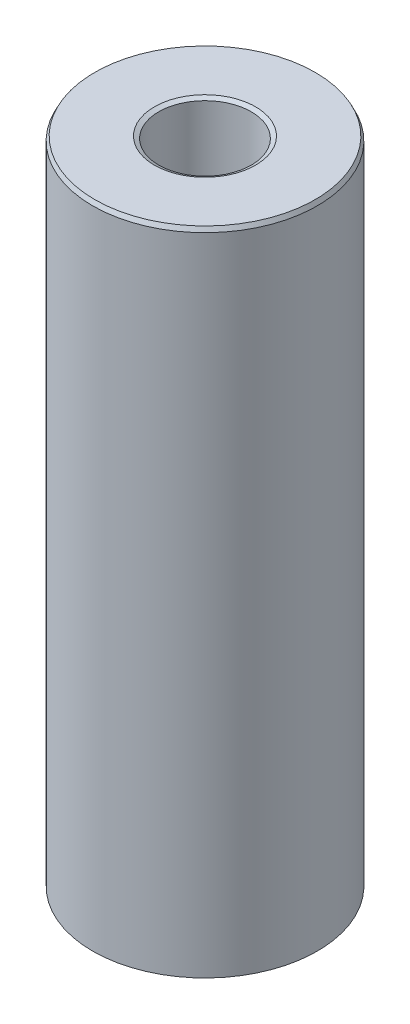
SolidWorks part; units mm, degrees
ref_plane "Front Plane" through (0, 0, 0) normal (0, 0, 1) x (1, 0, 0)
ref_plane "Top Plane" through (0, 0, 0) normal (0, 1, 0) x (1, 0, 0)
ref_plane "Right Plane" through (0, 0, 0) normal (1, 0, 0) x (0, 0, -1)
sketch "Sketch1" plane through (0, 0, 0) normal (0, 1, 0) x (1, 0, 0)
  circle A0 centre (0, 0) radius 32.5
  dimension "SLEEVE_OD" = 65
extrude "Boss-Extrude1" add sketch "Sketch1" along normal blind 188.5692
sketch "Sketch2" plane through (0, 0, 0) normal (0, 1, 0) x (1, 0, 0)
  circle A0 centre (0, 0) radius 13.3832
  dimension "BORE_D" = 26.7663
extrude "Cut-Extrude1" cut sketch "Sketch2" along normal through all
chamfer "Chamfer1" distance 1.2496 angle 26.174 4 edges at (0, 188.5692, 13.3832) (0, 0, 13.3832) (0, 0, 32.5) (0, 188.5692, 32.5) first distance on face at (0, 188.5692, 13.3832) first distance on face at (0, 0, 13.3832) first distance on face at (0, 188.5692, 32.5)
